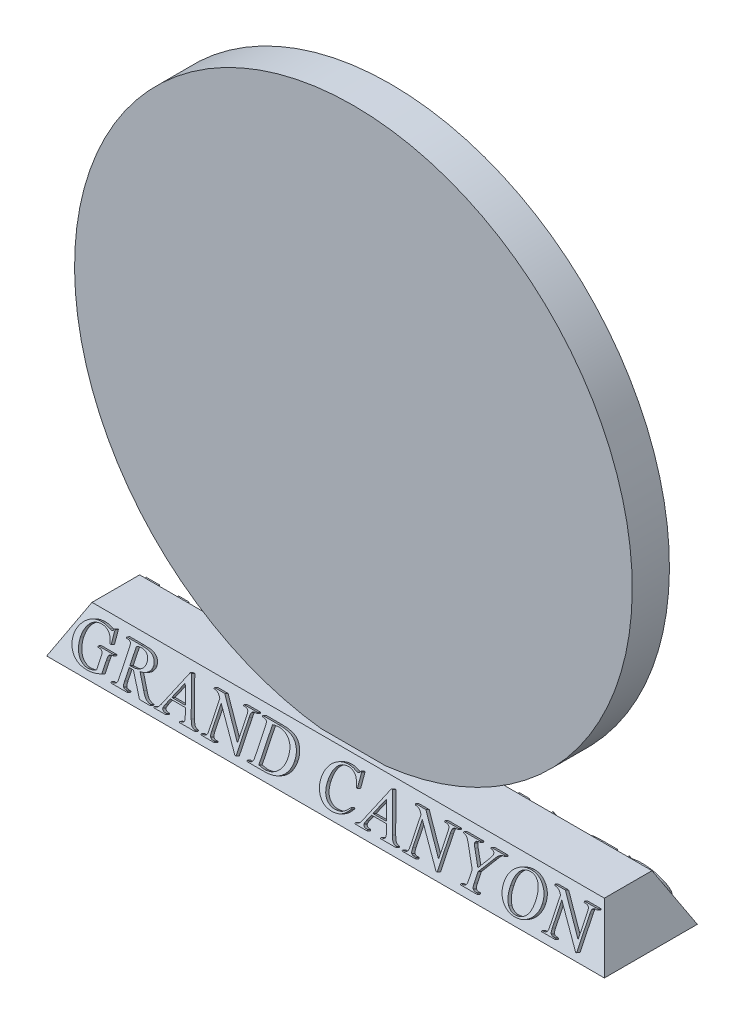
SolidWorks part; units mm, degrees
ref_plane "Front Plane" through (0, 0, 0) normal (0, 0, 1) x (1, 0, 0)
ref_plane "Top Plane" through (0, 0, 0) normal (0, 1, 0) x (1, 0, 0)
ref_plane "Right Plane" through (0, 0, 0) normal (1, 0, 0) x (0, 0, -1)
sketch "Sketch1" plane through (0, 0, 0) normal (0, 1, 0) x (1, 0, 0)
  line L1 (38.1, -6.35) -> (-38.1, -6.35)
  line L2 (38.1, -6.35) -> (38.1, 6.35)
  line L3 (38.1, 6.35) -> (-38.1, 6.35)
  line L4 (-38.1, -6.35) -> (-38.1, 6.35)
  line L5 (38.1, -6.35) -> (-38.1, 6.35) construction
  line L6 (38.1, 6.35) -> (-38.1, -6.35) construction
  point P0 (0, 0)
extrude "Boss-Extrude1" add sketch "Sketch1" along normal blind 6.35 draft 26
sketch "Sketch2" plane through (0, 0, 0) normal (0, 0, 1) x (1, 0, 0)
  circle A0 centre (0, 44.196) radius 38.1
extrude "Boss-Extrude2" add sketch "Sketch2" along normal blind 2.54 and the other way blind 2.54
sketch "Sketch5" plane through (0, 2.5019, 5.1297) normal (0, 0.4384, 0.8988) x (1, 0, 0)
  text T0 "GRAND CANYON" font "Times New Roman" height in points 20
sketch "Sketch6" plane through (0, 2.5019, -5.1297) normal (0, 0.4384, -0.8988) x (-1, 0, 0)
  text T0 "GRAND CANYON" font "Times New Roman" height in points 20
extrude "Boss-Extrude3" add sketch "Sketch5" along normal blind 0.508
extrude "Boss-Extrude4" add sketch "Sketch6" along normal blind 0.508
